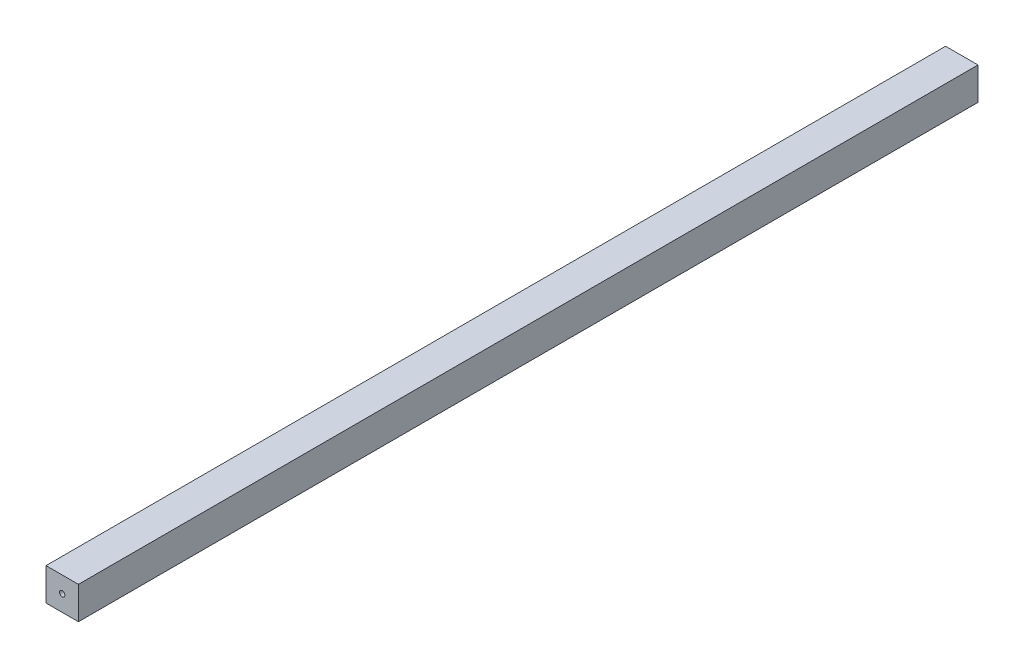
SolidWorks part; units mm, degrees
ref_plane "Front Plane" through (0, 0, 0) normal (0, 0, 1) x (1, 0, 0)
ref_plane "Top Plane" through (0, 0, 0) normal (0, 1, 0) x (1, 0, 0)
ref_plane "Right Plane" through (0, 0, 0) normal (1, 0, 0) x (0, 0, -1)
sketch "Sketch1" plane through (0, 0, 0) normal (0, 0, 1) x (1, 0, 0)
  line L1 (-12.7, -12.7) -> (12.7, -12.7)
  line L2 (-12.7, -12.7) -> (-12.7, 12.7)
  line L3 (-12.7, 12.7) -> (12.7, 12.7)
  line L4 (12.7, -12.7) -> (12.7, 12.7)
  line L5 (-12.7, -12.7) -> (12.7, 12.7) construction
  line L6 (-12.7, 12.7) -> (12.7, -12.7) construction
  point P0 (0, 0)
  dimension "D1" = 25.4
  dimension "D2" = 25.4
extrude "Boss-Extrude1" add sketch "Sketch1" along normal mid plane 704.85
sketch "Sketch2" plane through (0, 0, 352.425) normal (0, 0, 1) x (1, 0, 0)
  circle A0 centre (0, 0) radius 2.0828
  dimension "D1" = 4.1656
extrude "Cut-Extrude1" cut sketch "Sketch2" against normal blind 812.292
